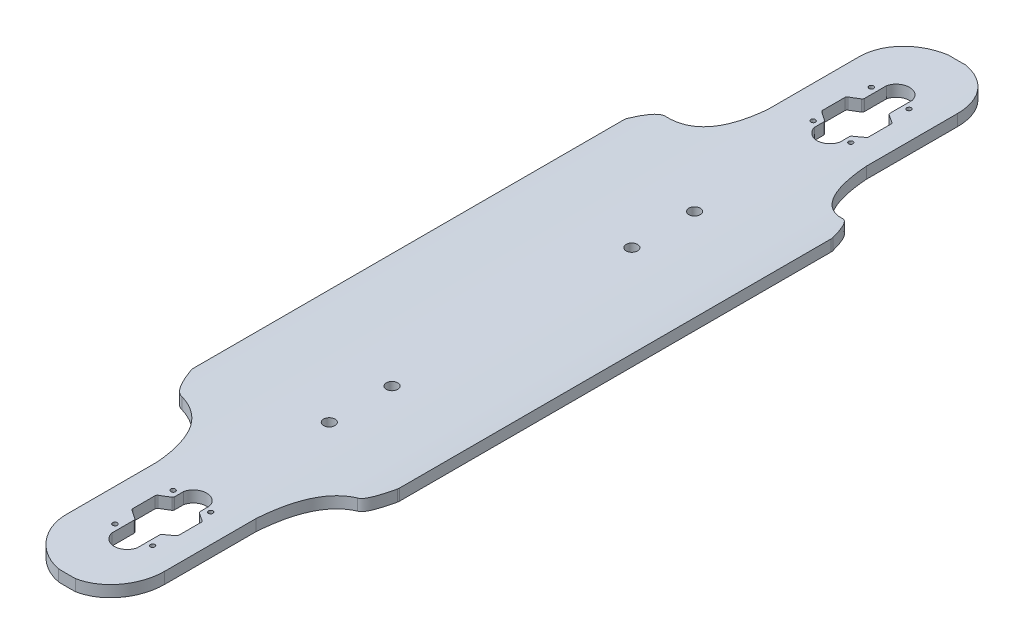
SolidWorks part; units mm, degrees
material "Maple"
ref_plane "Front Plane" through (0, 0, 0) normal (0, 0, 1) x (1, 0, 0)
ref_plane "Top Plane" through (0, 0, 0) normal (0, 1, 0) x (1, 0, 0)
ref_plane "Right Plane" through (0, 0, 0) normal (1, 0, 0) x (0, 0, -1)
sketch "Sketch1" plane through (0, 0, 0) normal (0, 0, 1) x (1, 0, 0)
  line L0 (0, 0) -> (230.1875, 0)
  line L1 (115.0937, 0) -> (115.0937, -12.7)
  line L2 (230.1875, 0) -> (230.1875, -12.7)
  line L3 (0, 0) -> (0, -12.7)
  arc A0 (230.1875, 0) -> (0, 0) centre (115.0938, 515.1686) cw
  arc A1 (230.1875, -12.7) -> (0, -12.7) centre (115.0938, 502.4686) cw
  point P6 (115.0937, -12.7)
  dimension "D1" = 2
extrude "Boss-Extrude1" add sketch "Sketch1" along normal blind 482.6 contours A1 L2 A0 L3 region at (115.0938, -14.8372, 0)
sketch "Sketch2" plane through (0, 0, 0) normal (0, 0, -1) x (-1, 0, 0)
  line L0 (-230.1875, 0) -> (-230.1875, -12.7)
  line L1 (0, 0) -> (0, -12.7)
  line L4 (-60.325, -19.05) -> (-60.325, -9.8511)
  line L5 (-169.8625, -19.05) -> (-169.8625, -9.8511)
  line L6 (-169.8625, -19.05) -> (-169.8625, -22.5511)
  line L7 (-60.325, -22.5511) -> (-60.325, -19.05)
  arc A0 (-230.1875, 0) -> (0, 0) centre (-115.0938, 515.1686) ccw
  arc A1 (-230.1875, -12.7) -> (0, -12.7) centre (-115.0938, 502.4686) ccw
  point P15 (-115.0938, -19.05)
  arc M1 (-230.1875, -12.7) -> (0, -12.7) centre (-115.0938, 502.4686) ccw
  line M2 (0, -12.7) -> (0, 0)
  arc M3 (0, 0) -> (-230.1875, 0) centre (-115.0938, 515.1686) cw
  line M4 (-230.1875, 0) -> (-230.1875, -12.7)
extrude "Boss-Extrude2" add sketch "Sketch2" along normal blind 98.425 contours L6 L5 M3 M4 M1 | L7 L4 M1 M2 M3 region at (200.025, -11.8738, 0) region at (30.1625, -11.8738, 0)
sketch "Sketch3" plane through (0, 0, 0) normal (0, 0, -1) x (-1, 0, 0)
  line L0 (-230.1875, -12.7) -> (-230.1875, 0)
  line L1 (0, 0) -> (0, -12.7)
  line L2 (-169.8625, -9.8511) -> (-169.8625, -22.5511)
  line L3 (-60.325, -9.8511) -> (-60.325, -22.5511)
  arc A0 (-230.1875, 0) -> (0, 0) centre (-115.0937, 515.1686) ccw
  arc A1 (-230.1875, -12.7) -> (0, -12.7) centre (-115.0938, 502.4686) ccw
  arc M1 (-169.8625, -22.5511) -> (-60.325, -22.5511) centre (-115.0938, 502.4686) ccw
  line M2 (-60.325, -22.5511) -> (-60.325, -9.8511)
  arc M3 (-60.325, -9.8511) -> (-169.8625, -9.8511) centre (-115.0938, 515.1686) cw
  line M4 (-169.8625, -9.8511) -> (-169.8625, -22.5511)
extrude "Boss-Extrude3" add sketch "Sketch3" along normal blind 254 contours M4 M1 M2 M3 region at (115.0938, -18.1014, 0)
sketch "Sketch4" plane through (0, 0, 482.6) normal (0, 0, 1) x (1, 0, 0)
  line L0 (0, 0) -> (0, -12.7)
  line L1 (230.1875, -12.7) -> (230.1875, 0)
  line L2 (60.325, -22.5511) -> (60.325, -9.8511)
  line L3 (169.8625, -22.5511) -> (169.8625, -9.8511)
  arc A0 (0, 0) -> (230.1875, 0) centre (115.0938, 515.1686) ccw
  arc A1 (0, -12.7) -> (230.1875, -12.7) centre (115.0938, 502.4686) ccw
  point P15 (115.0937, -19.05)
  arc M1 (0, -12.7) -> (230.1875, -12.7) centre (115.0938, 502.4686) ccw
  arc M3 (230.1875, 0) -> (0, 0) centre (115.0938, 515.1686) cw
extrude "Boss-Extrude4" add sketch "Sketch4" along normal blind 254 contours L3 L2 M1 M3 region at (115.0937, -18.1014, 482.6)
sketch "Sketch5" plane through (0, 0, 482.6) normal (0, 0, 1) x (1, 0, 0)
  line L0 (0, 0) -> (0, -12.7)
  line L1 (60.325, -9.8511) -> (60.325, -22.5511)
  line L2 (230.1875, 0) -> (230.1875, -12.7)
  line L3 (169.8625, -9.8511) -> (169.8625, -22.5511)
  arc A0 (0, 0) -> (230.1875, 0) centre (115.0938, 515.1686) ccw
  arc A1 (0, -12.7) -> (230.1875, -12.7) centre (115.0938, 502.4686) ccw
  arc M1 (0, -12.7) -> (60.325, -22.5511) centre (115.0938, 502.4686) ccw
  line M2 (60.325, -22.5511) -> (60.325, -9.8511)
  arc M3 (60.325, -9.8511) -> (0, 0) centre (115.0938, 515.1686) cw
  line M4 (0, 0) -> (0, -12.7)
extrude "Boss-Extrude5" add sketch "Sketch5" along normal blind 98.425 contours M4 M1 M2 M3 | L3 A1 L2 A0 region at (30.1625, -11.8738, 482.6) region at (200.025, -11.8738, 482.6)
ref_plane "Plane1" through (0, 0, 0) normal (0, -1, 0) x (-1, 0, 0)
sketch "Sketch6" plane through (0, 0, 0) normal (0, -1, 0) x (-1, 0, 0)
  line L0 (-115.0937, -736.6) -> (-115.0937, -482.6) construction
  line L1 (-169.8625, -736.6) -> (-60.325, -736.6) construction
  line L2 (-115.0938, 254) -> (-115.0937, 0) construction
  line L3 (-60.325, 254) -> (-169.8625, 254) construction
  line L4 (-230.1875, -482.6) -> (0, -482.6) construction
  line L5 (0, -581.025) -> (0, 98.425) construction
  line L6 (-230.1875, 0) -> (0, 0) construction
  line L7 (-60.325, -581.025) -> (0, -482.6) construction
  line L8 (-60.325, -736.6) -> (-60.325, -581.025) construction
  line L9 (-60.325, -682.625) -> (-169.8625, -682.625) construction
  line L10 (-169.8625, -736.6) -> (-169.8625, -581.025) construction
  line L11 (-169.8625, -581.025) -> (-230.1875, -482.6) construction
  line L12 (-60.325, 254) -> (-60.325, 98.425) construction
  line L13 (-60.325, 200.025) -> (-169.8625, 200.025) construction
  line L14 (-169.8625, 254) -> (-169.8625, 98.425) construction
  line L15 (-30.1625, -531.8125) -> (-200.025, -531.8125) construction
  line L16 (-230.1875, 0) -> (-169.8625, 98.425) construction
  line L17 (-60.325, 98.425) -> (0, 0) construction
  line L18 (-200.025, 49.2125) -> (-30.1625, 49.2125) construction
  line L19 (-30.1625, -531.8125) -> (-230.1875, -482.6) construction
  line L20 (-200.025, -531.8125) -> (0, -482.6) construction
  line L21 (0, 0) -> (-200.025, 49.2125) construction
  line L22 (-30.1625, 49.2125) -> (-230.1875, 0) construction
  line L23 (-230.1875, -510.9167) -> (0, -510.9167) construction
  line L24 (-230.1875, 28.3167) -> (0, 28.3167) construction
  line L25 (0, 0) -> (-8.6777, 28.3167) construction
  line L26 (-17.3554, -510.9167) -> (-8.6777, -510.9167) construction
  line L27 (-221.5098, 28.3167) -> (-230.1875, 0) construction
  line L28 (-8.6777, -510.9167) -> (0, -482.6) construction
  line L29 (-230.1875, -482.6) -> (-221.5098, -510.9167) construction
  line L30 (-212.8321, -510.9167) -> (-221.5098, -510.9167) construction
  line L31 (-8.6777, -510.9167) -> (0, -482.6) construction
  line L32 (-221.5098, -510.9167) -> (-230.1875, -482.6) construction
  line L33 (-17.3554, 28.3167) -> (-8.6777, 28.3167) construction
  line L34 (-8.6777, 28.3167) -> (0, 0) construction
  line L35 (-212.8321, 28.3167) -> (-221.5098, 28.3167) construction
  line L36 (-221.5098, 28.3167) -> (-230.1875, 0) construction
  line L38 (-60.325, -581.025) -> (0, -581.025)
  line L39 (0, -581.025) -> (0, -510.9167)
  line L40 (-60.325, -682.625) -> (-60.325, -736.6)
  line L41 (-60.325, -736.6) -> (-169.8625, -736.6)
  line L42 (-169.8625, -736.6) -> (-169.8625, -682.625)
  line L43 (-169.8625, -581.025) -> (-230.1875, -581.025)
  line L44 (-230.1875, -581.025) -> (-230.1875, -510.9167)
  line L45 (-230.1875, 0) -> (-230.1875, 98.425)
  line L46 (-230.1875, 98.425) -> (-169.8625, 98.425)
  line L47 (-169.8625, 200.025) -> (-169.8625, 254)
  line L48 (-169.8625, 254) -> (-60.325, 254)
  line L49 (-60.325, 254) -> (-60.325, 200.025)
  line L50 (-60.325, 98.425) -> (0, 98.425)
  line L51 (0, 98.425) -> (0, 0)
  line L52 (-230.1875, -482.6) -> (-230.1875, -510.9167)
  line L53 (0, -482.6) -> (0, -510.9167)
  arc A0 (-60.325, -682.625) -> (-169.8625, -682.625) centre (-115.0937, -682.625) cw
  arc A1 (-60.325, 200.025) -> (-169.8625, 200.025) centre (-115.0938, 200.025) ccw
  spline S0 degree 2 poles (-60.325, -581.025) (-55.0487, -517.0259) (-17.3554, -510.9167) knots 0 0 0 0.825721 0.825721 0.825721
  spline S1 degree 2 poles (-169.8625, -581.025) (-175.1388, -517.0259) (-212.8321, -510.9167) knots 0 0 0 0.825721 0.825721 0.825721
  spline S2 degree 2 poles (-169.8625, 98.425) (-175.1388, 34.4259) (-212.8321, 28.3167) knots 0 0 0 0.825721 0.825721 0.825721
  spline S3 degree 2 poles (-60.325, 98.425) (-55.0487, 34.4259) (-17.3554, 28.3167) knots 0 0 0 0.825721 0.825721 0.825721
  spline S4 degree 2 poles (-17.3554, -510.9167) (-8.6777, -510.9167) (0, -482.6) knots 0 0 0 1 1 1
  spline S5 degree 2 poles (-212.8321, -510.9167) (-221.5098, -510.9167) (-230.1875, -482.6) knots 0 0 0 1 1 1
  spline S6 degree 2 poles (-17.3554, 28.3167) (-8.6777, 28.3167) (0, 0) knots 0 0 0 1 1 1
  spline S7 degree 2 poles (-212.8321, 28.3167) (-221.5098, 28.3167) (-230.1875, 0) knots 0 0 0 1 1 1
  point P13 (-115.0937, -482.6)
  point P17 (-115.0937, 0)
  point P43 (-115.0938, -510.9167)
  point P44 (-17.3554, -510.9167)
  point P45 (-115.0938, 28.3167)
  point P49 (-115.0938, -510.9167)
  point P51 (-115.0938, 28.3167)
  point P53 (-212.8321, -510.9167)
  point P54 (-212.8321, 28.3167)
  point P55 (-17.3554, 28.3167)
extrude "Cut-Extrude1" cut sketch "Sketch6" along normal blind 98.425 contours L40 A0 L41 | L41 A0 L42 | S1 S5 L52 L44 L43 | S4 S0 L38 L39 L53 | S3 S6 L51 L50 | S7 S2 L46 L45 | A1 L48 L47 | A1 L49 L48 region at (25.0997, 0, 547.5668) region at (158.3996, 0, 724.4055) region at (71.7879, 0, 724.4055) region at (205.0878, 0, 547.5668) region at (205.0878, 0, -64.9668) region at (71.7879, 0, -241.8055) region at (158.3996, 0, -241.8055) region at (25.0997, 0, -64.9668)
sketch "Sketch8" plane through (0, 0, 0) normal (0, -1, 0) x (-1, 0, 0)
  line L0 (-60.325, 98.425) -> (-169.8625, 98.425) construction
  line L1 (0, 0) -> (-230.1875, 0) construction
  line L2 (-100.8698, 189.865) -> (-100.8698, 163.957)
  line L3 (-115.0938, 98.425) -> (-115.0937, 0)
  line L4 (0, -482.6) -> (-230.1875, -482.6)
  line L5 (0, -241.3) -> (-230.1875, -241.3)
  line L6 (0, -482.6) -> (0, 0) construction
  line L7 (-230.1875, -482.6) -> (-230.1875, 0) construction
  line L8 (-100.8698, 163.957) -> (-89.4398, 156.337)
  line L9 (-89.4398, 156.337) -> (-89.4398, 128.905)
  line L10 (-89.4398, 128.905) -> (-100.8698, 121.285)
  line L11 (-100.8698, 121.285) -> (-100.8698, 109.855)
  line L12 (-129.3177, 109.855) -> (-129.3177, 121.285)
  line L13 (-129.3177, 121.285) -> (-140.7477, 128.905)
  line L14 (-140.7477, 128.905) -> (-140.7477, 156.337)
  line L15 (-140.7477, 156.337) -> (-129.3177, 163.957)
  line L16 (-129.3177, 163.957) -> (-129.3177, 189.865)
  line L17 (-115.0938, 98.425) -> (-115.0938, 114.935) construction
  line L18 (-115.0938, 201.295) -> (-115.0938, 179.705) construction
  line L19 (-94.1388, 179.705) -> (-136.0488, 179.705) construction
  line L20 (-94.1388, 114.935) -> (-136.0488, 114.935) construction
  line L21 (-94.1387, -597.535) -> (-136.0487, -597.535) construction
  line L22 (-94.1387, -662.305) -> (-136.0487, -662.305) construction
  line L23 (-115.0937, -683.895) -> (-115.0937, -662.305) construction
  line L24 (-115.0937, -581.025) -> (-115.0937, -597.535) construction
  line L25 (-129.3177, -646.557) -> (-129.3177, -672.465)
  line L26 (-140.7477, -638.937) -> (-129.3177, -646.557)
  line L27 (-140.7477, -611.505) -> (-140.7477, -638.937)
  line L28 (-129.3177, -603.885) -> (-140.7477, -611.505)
  line L29 (-129.3177, -592.455) -> (-129.3177, -603.885)
  line L30 (-100.8698, -603.885) -> (-100.8698, -592.455)
  line L31 (-89.4398, -611.505) -> (-100.8698, -603.885)
  line L32 (-89.4398, -638.937) -> (-89.4398, -611.505)
  line L33 (-100.8698, -646.557) -> (-89.4398, -638.937)
  line L34 (-100.8698, -672.465) -> (-100.8698, -646.557)
  arc A0 (-100.8698, 189.865) -> (-129.3177, 189.865) centre (-115.0938, 186.7295) ccw
  arc A1 (-100.8698, 109.855) -> (-129.3177, 109.855) centre (-115.0938, 112.9905) cw
  circle A2 centre (-136.0488, 179.705) radius 2.54
  circle A3 centre (-136.0488, 114.935) radius 2.54
  circle A4 centre (-94.1388, 114.935) radius 2.54
  circle A5 centre (-94.1388, 179.705) radius 2.54
  circle A6 centre (-94.1387, -597.535) radius 2.54
  circle A7 centre (-136.0487, -597.535) radius 2.54
  circle A8 centre (-136.0487, -662.305) radius 2.54
  arc A9 (-100.8698, -592.455) -> (-129.3177, -592.455) centre (-115.0937, -595.5905) ccw
  arc A10 (-100.8698, -672.465) -> (-129.3177, -672.465) centre (-115.0937, -669.3295) cw
  circle A11 centre (-94.1387, -662.305) radius 2.54
  point P26 (-115.0937, 189.865)
  point P29 (-115.0938, 201.295)
  point P30 (-115.0938, 98.425)
  point P42 (-115.0938, 179.705)
  point P46 (-115.0938, 114.935)
  point P47 (-100.8698, 163.957)
  point P48 (-89.4398, 156.337)
  point P49 (-89.4398, 128.905)
  point P50 (-100.8698, 121.285)
  point P51 (-100.8698, 109.855)
  point P52 (-129.3177, 109.855)
  point P53 (-129.3177, 121.285)
  point P54 (-140.7477, 128.905)
  point P55 (-140.7477, 156.337)
  point P56 (-129.3177, 163.957)
  point P57 (-129.3177, 189.865)
  point P58 (-100.8698, 189.865)
  point P59 (-100.8698, 163.957)
  point P60 (-89.4398, 156.337)
  point P87 (-115.0937, -672.465)
extrude "Cut-Extrude2" cut sketch "Sketch8" along normal blind 30.48 contours A1 L11 L10 L9 L8 L2 A0 L16 L15 L14 L13 L12 | A4 | A10 L34 L33 L32 L31 L30 A9 L29 L28 L27 L26 L25 | A2 | A5 | A3 | A11 | A8 | A6 | A7 region at (115.0937, 0, -148.2319) region at (115.0937, 0, 630.8319) region at (94.1388, 0, -114.935)
fillet "Fillet2" radius 2.54 16 edges at (100.8698, -18.8583, -121.285) (89.4398, -18.4262, -128.905) (89.4398, -18.4262, -156.337) (100.8698, -18.8583, -163.957) (129.3177, -18.8583, -121.285) (140.7477, -18.4262, -128.905) (140.7477, -18.4262, -156.337) (129.3177, -18.8583, -163.957) (140.7477, -18.4262, 638.937) (140.7477, -18.4262, 611.505) (89.4398, -18.4262, 638.937) (89.4398, -18.4262, 611.505) (129.3177, -18.8583, 646.557) (129.3177, -18.8583, 603.885) (100.8698, -18.8583, 646.557) (100.8698, -18.8583, 603.885)
fillet "Fillet1" radius 7.62 4 edges at (0, -6.35, 0) (0, -6.35, 482.6) (230.1875, -6.35, 0) (230.1875, -6.35, 482.6)
sketch "Sketch9" plane through (0, 0, 0) normal (0, -1, 0) x (-1, 0, 0)
  line L0 (-115.0937, -736.6) -> (-115.0938, -88.7823) construction
  line L1 (-124.3844, -736.6) -> (-105.8031, -736.6) construction
  line L2 (-105.8031, 254) -> (-124.3844, 254) construction
  line L3 (0, -481.4477) -> (-230.1875, -481.4477) construction
  line L4 (-230.1875, -1.1523) -> (0, -1.1523) construction
  line L5 (-115.0937, -481.4477) -> (-115.0938, -470.0177) construction
  line L6 (-115.0938, -470.0177) -> (-115.0938, -400.1677) construction
  line L7 (0, -241.3) -> (-230.1875, -241.3) construction
  line L8 (0, -481.4477) -> (0, -1.1523) construction
  line L9 (-230.1875, -481.4477) -> (-230.1875, -1.1523) construction
  line L10 (-115.0938, -76.0823) -> (-115.0938, 254) construction
  circle A4 centre (-115.0938, -444.6177) radius 6.35
  circle A5 centre (-115.0938, -374.7677) radius 6.35
  circle A6 centre (-115.0938, -107.8323) radius 6.35
  circle A7 centre (-115.0938, -37.9823) radius 6.35
  point P23 (-115.0937, -82.4323)
  point P24 (-115.0937, -12.5823)
extrude "Cut-Extrude3" cut sketch "Sketch9" along normal blind 38.1
sketch "Sketch10" plane through (0, 0, 0) normal (0, -1, 0) x (-1, 0, 0)
  line L0 (0, -481.4477) -> (-230.1875, -481.4477) construction
  line L1 (-230.1875, -1.1523) -> (0, -1.1523) construction
  line L2 (0, -241.3) -> (-230.1875, -241.3) construction
  line L3 (0, -481.4477) -> (0, -1.1523) construction
  line L4 (-230.1875, -481.4477) -> (-230.1875, -1.1523) construction
  line L5 (-140.4937, -481.4477) -> (-89.6937, -481.4477)
  line L6 (-96.0437, -487.7977) -> (-1.6735, -487.7977)
  line L7 (-134.1437, -487.7977) -> (-228.514, -487.7977)
  line L10 (-134.1437, -487.7977) -> (-140.4937, -481.4477)
  line L11 (-96.0437, -487.7977) -> (-89.6937, -481.4477)
  line L12 (-134.1437, 5.1977) -> (-140.4937, -1.1523)
  line L13 (-134.1437, 5.1977) -> (-228.514, 5.1977)
  line L14 (-140.4937, -1.1523) -> (-89.6937, -1.1523)
  line L15 (-96.0438, 5.1977) -> (-89.6937, -1.1523)
  line L16 (-96.0438, 5.1977) -> (-1.6735, 5.1977)
  parabola Q0 (-0.3473, -483.7219) -> (-17.3554, -510.9167) focus (-17.3554, -508.2574) apex (-17.3554, -510.9167) construction
  parabola Q1 (-229.8402, -483.7219) -> (-212.8321, -510.9167) focus (-212.8321, -508.2574) apex (-212.8321, -510.9167) construction
  point P17 (-115.0937, -481.4477)
  point P20 (-89.6937, -481.4477)
  point P24 (-140.4937, -481.4477)
